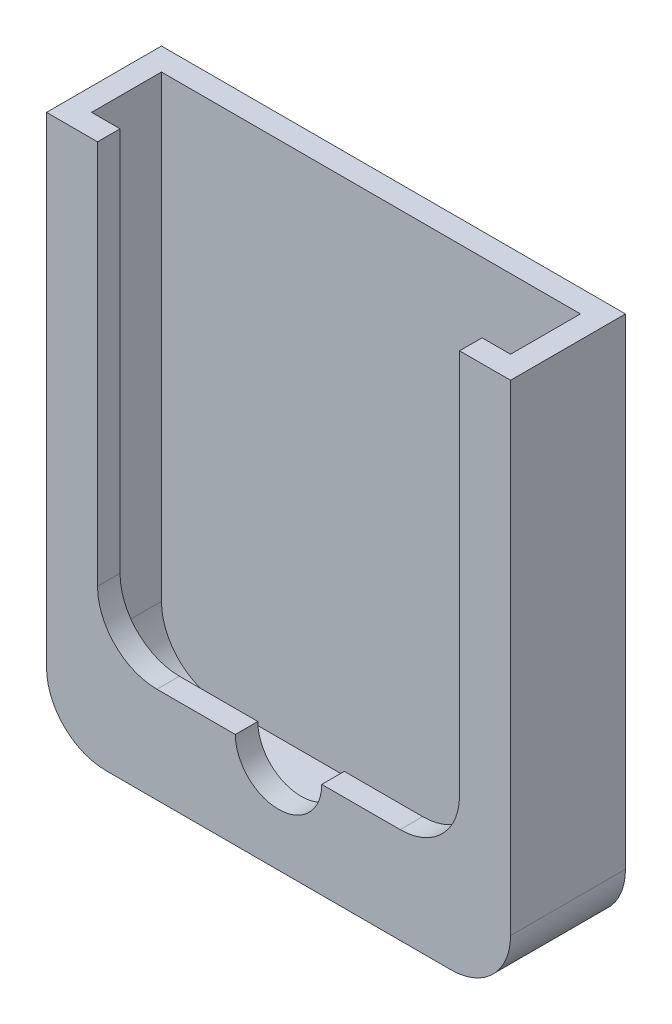
SolidWorks part; units mm, degrees
ref_plane "Front Plane" through (0, 0, 0) normal (0, 0, 1) x (1, 0, 0)
ref_plane "Top Plane" through (0, 0, 0) normal (0, 1, 0) x (1, 0, 0)
ref_plane "Right Plane" through (0, 0, 0) normal (1, 0, 0) x (0, 0, -1)
sketch "Sketch1" plane through (0, 0, 0) normal (0, 0, 1) x (1, 0, 0)
  line L1 (0, 0) -> (65.4304, 0)
  line L2 (0, 0) -> (0, 76.2)
  line L3 (0, 76.2) -> (65.4304, 76.2)
  line L4 (65.4304, 0) -> (65.4304, 76.2)
  dimension "D1" = 65.4304
  dimension "D2" = 76.2
extrude "Boss-Extrude1" add sketch "Sketch1" along normal mid plane 16.2052
sketch "Sketch2" plane through (0, 76.2, 0) normal (0, 1, 0) x (1, 0, 0)
  line L0 (3.175, 4.9276) -> (62.2554, 4.9276)
  line L1 (62.2554, 4.9276) -> (62.2554, -4.9276)
  line L2 (3.175, -4.9276) -> (62.2554, -4.9276)
  line L3 (65.4304, -8.1026) -> (0, -8.1026) construction
  line L8 (3.175, -4.9276) -> (3.175, 4.9276)
  line L9 (65.4304, 8.1026) -> (0, 8.1026) construction
  line L10 (0, -8.1026) -> (0, 8.1026) construction
  line L11 (65.4304, -8.1026) -> (65.4304, 8.1026) construction
  line L12 (32.7152, 14.3046) -> (32.7152, -12.4638) construction
  point P17 (32.7152, 4.9276)
  dimension "D1" = 3.175
  dimension "D2" = 3.175
  dimension "D3" = 3.175
  dimension "D4" = 3.175
extrude "Cut-Extrude1" cut sketch "Sketch2" against normal offset from surface (73.025 mm away) 3.175 up to face at (32.7152, 0, 0)
sketch "Sketch3" plane through (0, 76.2, 0) normal (0, 1, 0) x (1, 0, 0)
  line L0 (65.4304, -8.1026) -> (0, -8.1026) construction
  line L1 (7.1882, -8.1026) -> (58.2422, -8.1026)
  line L2 (7.1882, -8.1026) -> (7.1882, -4.9276)
  line L3 (7.1882, -4.9276) -> (58.2422, -4.9276)
  line L4 (58.2422, -8.1026) -> (58.2422, -4.9276)
  line L5 (3.175, -4.9276) -> (62.2554, -4.9276) construction
  line L6 (32.7152, 12.6207) -> (32.7152, -18.9707) construction
  line L7 (65.4304, 8.1026) -> (0, 8.1026) construction
  point P13 (32.7152, 8.1026)
  dimension "D1" = 51.054
extrude "Cut-Extrude2" cut sketch "Sketch3" against normal offset from surface (62.6618 mm away) 13.5382 up to face at (32.7152, 0, 0)
fillet "Fillet1" radius 8.382 4 edges at (62.2554, 3.175, 0) (3.175, 3.175, 0) (7.1882, 13.5382, 6.5151) (58.2422, 13.5382, 6.5151)
fillet "Fillet2" radius 8.382 2 edges at (0, 0, 0) (65.4304, 0, 0)
sketch "Sketch4" plane through (0, 0, 8.1026) normal (0, 0, 1) x (1, 0, 0)
  line L0 (49.8602, 13.5382) -> (15.5702, 13.5382) construction
  circle A0 centre (32.7152, 13.5382) radius 6.096
  dimension "D1" = 12.192
extrude "Cut-Extrude3" cut sketch "Sketch4" against normal up to next
equation "\"width\"= 2.306in'Phone width"
equation "\"D1@Sketch1\" = \"width\" + 2 * \"wall\" + 2 * \"margin\"'Overall width of holster"
equation "\"wall\"= 0.125in'Metal thickness"
equation "\"height\"= 3in'Overall holster height"
equation "\"D2@Sketch1\"= \"height\"'Overall holster height"
equation "\"depth\"= 0.368in'Thickness of phone"
equation "\"D1@Boss-Extrude1\"= \"depth\" + 2 * \"wall\" + 2 * \"margin\" 'Overal depth of holster"
equation "\"D3@Sketch2\"=\"wall\""
equation "\"D4@Sketch2\"= \"wall\""
equation "\"screen_width\"= 2.01in'Width of visible screen"
equation "\"margin\"= 0.01in'Slop to allow the phone to fit properly"
equation "\"D2@Sketch2\" = \"wall\""
equation "\"D1@Sketch2\"=\"wall\""
equation "\"D1@Cut-Extrude1\"=\"wall\""
equation "\"D1@Sketch3\"=\"screen_width\""
equation "\"D1@Cut-Extrude2\" = \"lower_edge\" + \"wall\""
equation "\"lower_edge\"= .408'How deep the phone sits in the holster"
equation "\"tool_diam\"= .66'Diameter of the tool used for undercuts, set to match the corners of the phone"
equation "\"D1@Fillet1\"=\"tool_diam\"/2"
equation "\"D1@Fillet2\"=\"tool_diam\"/2"
equation "\"button_cutout\"= .48in'Cutout for the iPhone button"
equation "\"D1@Sketch4\" = \"button_cutout\""
